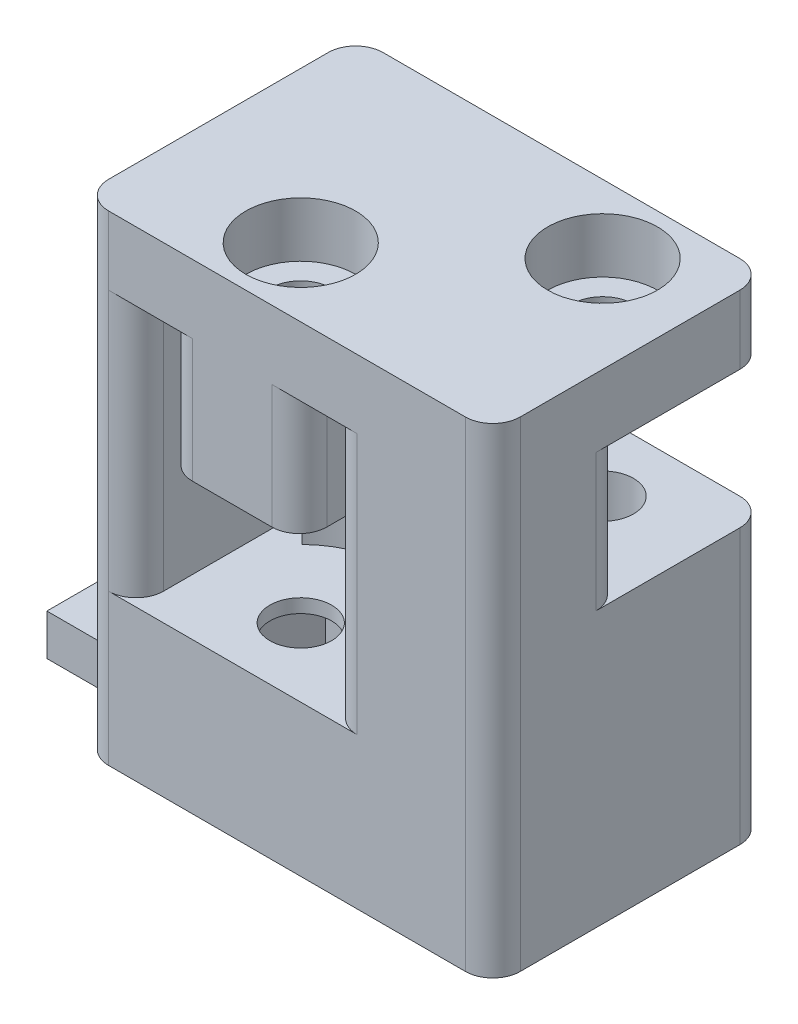
SolidWorks part; units mm, degrees
material "ABS"
ref_plane "Front Plane" through (0, 0, 0) normal (0, 0, 1) x (1, 0, 0)
ref_plane "Top Plane" through (0, 0, 0) normal (0, 1, 0) x (1, 0, 0)
ref_plane "Right Plane" through (0, 0, 0) normal (1, 0, 0) x (0, 0, -1)
sketch "Sketch1" plane through (0, 0, 0) normal (0, 1, 0) x (1, 0, 0)
  line L1 (-15, -10) -> (15, -10)
  line L2 (-15, -10) -> (-15, 10)
  line L3 (-15, 10) -> (15, 10)
  line L4 (15, -10) -> (15, 10)
  line L5 (-15, -10) -> (15, 10) construction
  line L6 (-15, 10) -> (15, -10) construction
  point P0 (0, 0)
  dimension "D1" = 30
  dimension "D2" = 20
extrude "Boss-Extrude1" add sketch "Sketch1" along normal blind 11
sketch "Sketch2" plane through (0, 11, 0) normal (0, 1, 0) x (1, 0, 0)
  line L0 (15, -10) -> (15, 10) construction
  line L1 (-15, -10) -> (15, -10) construction
  line L2 (-11, 10) -> (-11, -10)
  line L3 (15, 10) -> (-15, 10) construction
  line L4 (-8.899, -10) -> (-8.899, 10)
  line L5 (-8.899, 10) -> (-11, 10)
  line L6 (0.899, -10) -> (0.899, 10)
  line L7 (0.899, 10) -> (3.101, 10)
  line L8 (3.101, 10) -> (3.101, -10)
  line L9 (3.101, -10) -> (0.899, -10)
  line L10 (-11, -10) -> (-8.899, -10)
  circle A0 centre (-4, -5) radius 7
  circle A1 centre (8, 5) radius 7
  dimension "D1" = 14
  dimension "D2" = 14
  dimension "D3" = 12
  dimension "D4" = 7
  dimension "D5" = 10
  dimension "D6" = 5
extrude "Boss-Extrude2" add sketch "Sketch2" along normal blind 19
sketch "Sketch3" plane through (0, 30, 0) normal (0, 1, 0) x (1, 0, 0)
  line L1 (-15, 10) -> (15, 10)
  line L2 (-15, 10) -> (-15, -10)
  line L3 (-15, -10) -> (15, -10)
  line L4 (15, 10) -> (15, -10)
extrude "Boss-Extrude3" add sketch "Sketch3" along normal blind 5
sketch "Sketch4" plane through (0, 30, 0) normal (0, -1, 0) x (1, 0, 0)
  line L0 (-8.899, 0) -> (-8.899, 10)
  line L1 (-11, 10) -> (3.101, 10) construction
  line L2 (0.899, 0) -> (0.899, 10)
  line L3 (0.899, 10) -> (-8.899, 10)
  arc A0 (0.899, 0) -> (-8.899, 0) centre (-4, 5) cw
extrude "Boss-Extrude4" add sketch "Sketch4" along normal blind 9
sketch "Sketch5" plane through (0, 11, 0) normal (0, 1, 0) x (1, 0, 0)
  line L1 (-8.899, 0) -> (0.899, -10) construction
  line L3 (15, 10) -> (15, 5)
  line L4 (15, 10) -> (0.899, 10)
  line L5 (0.899, 10) -> (0.899, 0)
  line L6 (-11, -10) -> (3.101, -10) construction
  line L7 (0.899, 0) -> (-8.899, -10) construction
  line L8 (3.101, 0) -> (3.101, -10) construction
  line L10 (3.101, -5.2404) -> (3.101, 0)
  arc A0 (15, 5) -> (3.101, 0) centre (8, 5) cw
  arc A3 (0.899, 0) -> (3.101, -5.2404) centre (-4.2356, -5.2404) cw
extrude "Boss-Extrude5" add sketch "Sketch5" along normal blind 9
sketch "Sketch6" plane through (0, 20, 0) normal (0, 1, 0) x (1, 0, 0)
  line L0 (0.899, 10) -> (0.899, 0) construction
  line L2 (3.101, 0) -> (3.101, -5.2404)
  line L3 (0.899, 0) -> (0.899, 5.2404)
  arc A1 (0.899, 0) -> (3.101, -5.2404) centre (-4.2356, -5.2404) cw
  arc A2 (3.101, 0) -> (0.899, 5.2404) centre (8.2356, 5.2404) cw
extrude "Boss-Extrude6" add sketch "Sketch6" along normal blind 1
fillet "Fillet1" radius 2 8 edges at (15, 25, -5) (0.899, 25, -10) (-11, 20.5, -10) (-11, 20.5, 10) (-8.899, 20.5, -10) (3.101, 20.5, 10) (0.899, 25.5, 10) (-8.899, 25.5, 10)
sketch "Sketch7" plane through (0, 35, 0) normal (0, 1, 0) x (1, 0, 0)
  line L0 (-15, -10) -> (15, -10) construction
  line L1 (15, -10) -> (15, 10) construction
  circle A0 centre (-4, -5) radius 2.25
  circle A1 centre (8, 5) radius 2.25
  dimension "D4" = 4.5
  dimension "D5" = 4.5
  dimension "D1" = 12
  dimension "D2" = 10
  dimension "D3" = 5
  dimension "D6" = 7
extrude "Cut-Extrude1" cut sketch "Sketch7" against normal through all
sketch "Sketch9" plane through (0, 35, 0) normal (0, 1, 0) x (1, 0, 0)
  line L1 (3.0925, 5) -> (5.5463, 0.75)
  line L2 (5.5463, 0.75) -> (10.4537, 0.75)
  line L3 (10.4537, 0.75) -> (12.9075, 5)
  line L4 (12.9075, 5) -> (10.4537, 9.25)
  line L5 (10.4537, 9.25) -> (5.5463, 9.25)
  line L6 (5.5463, 9.25) -> (3.0925, 5)
  line L7 (-8.9075, -5) -> (-6.4537, -9.25)
  line L8 (-6.4537, -9.25) -> (-1.5463, -9.25)
  line L9 (-1.5463, -9.25) -> (0.9075, -5)
  line L10 (0.9075, -5) -> (-1.5463, -0.75)
  line L11 (-1.5463, -0.75) -> (-6.4537, -0.75)
  line L12 (-6.4537, -0.75) -> (-8.9075, -5)
  circle A0 centre (8, 5) radius 4.25 construction
  circle A1 centre (-4, -5) radius 4.25 construction
  dimension "D1" = 8.5
  dimension "D2" = 8.5
extrude "Cut-Extrude3" [suppressed] cut sketch "Sketch9" against normal blind 10
hole_wizard "CBORE for M4 Hex Socket Head Cap Screw2" positions "Sketch10" profile "Sketch11" counterbore size "M4" standard "ISO" end condition through all
sketch "Sketch10" plane through (0, 35, 0) normal (0, 1, 0) x (1, 0, 0)
  point P0 (-4, -5)
  point P3 (8, 5)
sketch "Sketch11" plane through (-4, 35, 5) normal (1, 0, 0) x (0, 0, 1)
  line L0 (0, 0) -> (0, 35)
  line L1 (0, 35) -> (2.25, 35)
  line L3 (2.25, 35) -> (2.25, 4)
  line L4 (2.25, 4) -> (4, 4)
  line L5 (4, 4) -> (4, 0)
  line L7 (4, 0) -> (0, 0)
  line L11 (0, -6.35) -> (0, 107.95) construction
  dimension "Thru Hole Dia." = 4.5
  dimension "Thru Hole Depth" = 35
  dimension "C'Bore Dia." = 8
  dimension "C'Bore Depth" = 4
sketch "Sketch12" plane through (0, 0, 0) normal (0, -1, 0) x (1, 0, 0)
  line L1 (0.9075, 5) -> (-1.5463, 9.25)
  line L2 (-1.5463, 9.25) -> (-6.4537, 9.25)
  line L3 (-6.4537, 9.25) -> (-8.9075, 5)
  line L4 (-8.9075, 5) -> (-6.4537, 0.75)
  line L5 (-6.4537, 0.75) -> (-1.5463, 0.75)
  line L6 (-1.5463, 0.75) -> (0.9075, 5)
  line L7 (3.0925, -5) -> (5.5463, -9.25)
  line L8 (5.5463, -9.25) -> (10.4537, -9.25)
  line L9 (10.4537, -9.25) -> (12.9075, -5)
  line L10 (12.9075, -5) -> (10.4537, -0.75)
  line L11 (10.4537, -0.75) -> (5.5463, -0.75)
  line L12 (5.5463, -0.75) -> (3.0925, -5)
  circle A0 centre (-4, 5) radius 4.25 construction
  circle A1 centre (8, -5) radius 4.25 construction
  dimension "D2" = 8.5
  dimension "D1" = 8.5
extrude "Cut-Extrude4" cut sketch "Sketch12" against normal blind 10
hole_wizard "CBORE for M4 Hex Socket Head Cap Screw1" [suppressed] positions "Sketch15" profile "Sketch16" counterbore size "M4" standard "ISO"
sketch "Sketch15" plane through (0, 0, 0) normal (0, -1, 0) x (-1, 0, 0)
  point P0 (-8, 5)
  point P3 (4, -5)
sketch "Sketch16" plane through (8, 0, -5) normal (1, 0, 0) x (0, 0, -1)
  line L0 (0, 0) -> (0, 35)
  line L1 (0, 35) -> (2.25, 35)
  line L3 (2.25, 35) -> (2.25, 4)
  line L4 (2.25, 4) -> (4, 4)
  line L5 (4, 4) -> (4, 0)
  line L7 (4, 0) -> (0, 0)
  line L11 (0, -6.35) -> (0, 107.95) construction
  dimension "Thru Hole Dia." = 4.5
  dimension "Thru Hole Depth" = 35
  dimension "C'Bore Dia." = 8
  dimension "C'Bore Depth" = 4
sketch "Sketch18" plane through (-15, 0, 0) normal (-1, 0, 0) x (0, 0, 1)
  line L0 (-10, 35) -> (10, 35) construction
  line L1 (5.5, 35) -> (-5.5, 35)
  line L2 (5.5, 35) -> (5.5, 32)
  line L3 (5.5, 32) -> (-5.5, 32)
  line L4 (-5.5, 35) -> (-5.5, 32)
  line L5 (-10, 35) -> (-10, 0) construction
  dimension "D1" = 3
  dimension "D2" = 11
  dimension "D3" = 4.5
extrude "Boss-Extrude8" [suppressed] add sketch "Sketch18" along normal blind 7
sketch "Sketch19" [suppressed] plane through (0, 32, 0) normal (0, -1, 0) x (1, 0, 0)
  line L0 (-22, -5.5) -> (-15, -5.5) construction
  line L1 (-15, -5.5) -> (-15, 5.5) construction
  circle A0 centre (-18.5, 0) radius 1.75
  dimension "D1" = 3.5
  dimension "D2" = 5.5
  dimension "D3" = 3.5
extrude "Cut-Extrude5" [suppressed] cut sketch "Sketch19" against normal blind 6
sketch "Sketch20" [suppressed] plane through (0, 32, 0) normal (0, -1, 0) x (1, 0, 0)
  circle A0 centre (-18.5, 0) radius 3
  dimension "D1" = 6
extrude "Cut-Extrude6" [suppressed] cut sketch "Sketch20" against normal blind 1
sketch "Sketch23" plane through (-15, 0, 0) normal (-1, 0, 0) x (0, 0, 1)
  line L0 (-10, 0) -> (10, 0) construction
  line L1 (-5.5, 0) -> (5.5, 0)
  line L2 (-5.5, 0) -> (-5.5, 3)
  line L3 (-5.5, 3) -> (5.5, 3)
  line L4 (5.5, 0) -> (5.5, 3)
  line L5 (10, 35) -> (10, 0) construction
  dimension "D1" = 3
  dimension "D2" = 11
  dimension "D3" = 4.5
extrude "Boss-Extrude10" add sketch "Sketch23" along normal blind 7
sketch "Sketch24" plane through (0, 3, 0) normal (0, 1, 0) x (1, 0, 0)
  line L0 (-22, -5.5) -> (-22, 5.5) construction
  circle A0 centre (-18.5, 0) radius 1.75
  dimension "D1" = 3.5
  dimension "D2" = 3.5
extrude "Cut-Extrude7" cut sketch "Sketch24" against normal blind 7
sketch "Sketch25" plane through (0, 3, 0) normal (0, 1, 0) x (1, 0, 0)
  circle A0 centre (-18.5, 0) radius 3
  dimension "D1" = 6
extrude "Cut-Extrude8" cut sketch "Sketch25" against normal blind 1
fillet "Fillet2" radius 2 5 edges at (15, 10, -10) (15, 32.5, -10) (15, 17.5, 10) (-15, 17.5, 10) (-15, 17.5, -10)
